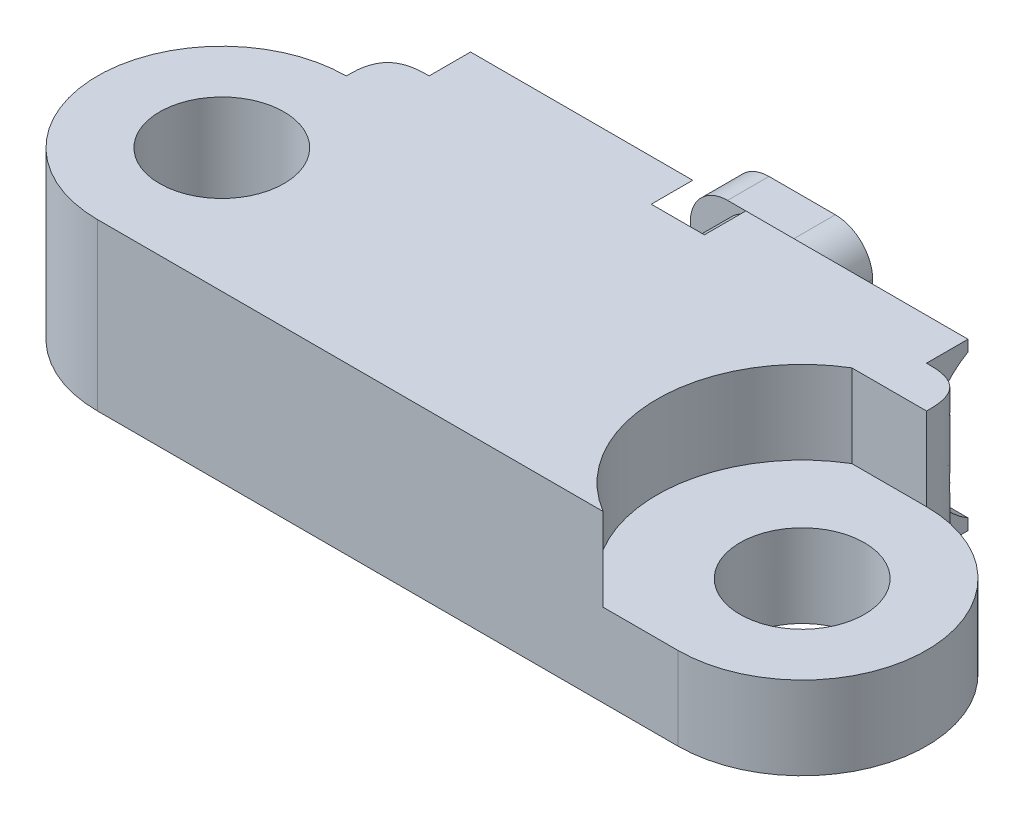
SolidWorks part; units mm, degrees
ref_plane "Front Plane" through (0, 0, 0) normal (0, 0, 1) x (1, 0, 0)
ref_plane "Top Plane" through (0, 0, 0) normal (0, 1, 0) x (1, 0, 0)
ref_plane "Right Plane" through (0, 0, 0) normal (1, 0, 0) x (0, 0, -1)
sketch "Sketch1" plane through (0, 0, 0) normal (0, 1, 0) x (1, 0, 0)
  line L0 (-7, 0) -> (7, 0) construction
  line L1 (-7, 3) -> (7, 3)
  line L2 (-7, -3) -> (7, -3)
  arc A0 (-7, 3) -> (-7, -3) centre (-7, 0) ccw
  arc A1 (7, -3) -> (7, 3) centre (7, 0) ccw
  circle A2 centre (-7, 0) radius 1.5
  circle A3 centre (7, 0) radius 1.5
  point P3 (0, 0)
  point P9 (-10, 0)
  point P10 (10, 0)
  dimension "D3" = 3
  dimension "D4" = 3
  dimension "D1" = 6
  dimension "D2" = 20
extrude "Boss-Extrude1" add sketch "Sketch1" along normal mid plane 4
sketch "Sketch2" plane through (0, 2, 0) normal (0, 1, 0) x (1, 0, 0)
  line L0 (5.1972, 3) -> (7, 3)
  line L1 (7, 3) -> (-7, 3) construction
  line L2 (-7, -3) -> (7, -3) construction
  line L3 (7, -3) -> (5.1972, -3)
  arc A0 (7, 3) -> (7, -3) centre (7, 0) cw
  arc A1 (5.1972, -3) -> (5.1972, 3) centre (7, 0) cw
  dimension "D1" = 3.5
extrude "Cut-Extrude1" cut sketch "Sketch2" against normal blind 2
sketch "Sketch3" plane through (0, -2, 0) normal (0, -1, 0) x (1, 0, 0)
  line L0 (7, -3) -> (7, -4)
  line L1 (7, -4) -> (-7, -4)
  line L2 (-7, -4) -> (-7, -3)
  line L3 (-7, -3) -> (7, -3)
  dimension "D1" = 1
extrude "Boss-Extrude2" add sketch "Sketch3" against normal up to surface (4 mm away) up to face at (-2.0757, 2, 0)
fillet "Fillet1" radius 1 2 edges at (7, 0, -4) (-7, 0, -4) curvature continuous yes
sketch "Sketch4" plane through (0, 0, 0) normal (1, 0, 0) x (0, 0, -1)
  line L0 (4, 0) -> (6, 0) construction
  line L2 (4, 2) -> (6, 2) construction
  line L3 (4, 2) -> (5, 2)
  line L4 (5, 2) -> (5, 1.7321)
  line L5 (5, -2) -> (5, -1.7321)
  line L6 (4, -2) -> (5, -2)
  line L7 (4, 2) -> (4, -2)
  arc A1 (5, -1.7321) -> (5, 1.7321) centre (6, 0) cw
  dimension "D2" = 2
  dimension "D1" = 1
extrude "Boss-Extrude3" add sketch "Sketch4" along normal up to vertex (6 mm away) and the other way up to vertex (6 mm away) contours L7 A1 L4 L3 | L5 A1 L7 L6 region at (0, -1.512, -4.3568) region at (0, 1.512, -4.3568) up to point (6, -2, -4) other way up to point (-6, 2, -4)
sketch "Sketch5" plane through (0, 0, 0) normal (0, 0, 1) x (1, 0, 0)
  line L0 (-11.6879, 0) -> (13.8393, 0) construction
  circle A0 centre (0, 0) radius 2.1
  dimension "D1" = 4.2
extrude "Cut-Extrude4" cut sketch "Sketch5" against normal blind 10 from vertex starting at point (6, 0, -4)
sketch "Sketch6" plane through (0, 0, -4) normal (0, 0, -1) x (-1, 0, 0)
  line L0 (0, 1) -> (-0.8, 1)
  line L1 (-1.7, 0.1) -> (-1.7, -0.1)
  line L2 (-0.8, -1) -> (0, -1)
  line L3 (0, -1) -> (0.8, -1)
  line L4 (1.7, -0.1) -> (1.7, 0.1)
  line L5 (0.8, 1) -> (0, 1)
  circle A0 centre (0, 0) radius 1
  arc A1 (1.7, 0.1) -> (0.8, 1) centre (0.8, 0.1) ccw
  arc A2 (0.8, -1) -> (1.7, -0.1) centre (0.8, -0.1) ccw
  arc A3 (-1.7, -0.1) -> (-0.8, -1) centre (-0.8, -0.1) ccw
  arc A4 (-0.8, 1) -> (-1.7, 0.1) centre (-0.8, 0.1) ccw
  point P17 (-1.7, 1)
  dimension "D1" = 2
  dimension "D3" = 0.9
  dimension "D2" = 0.8
  dimension "D4" = 0.8
extrude "Boss-Extrude5" add sketch "Sketch6" along normal blind 3 contours A0 region at (0, 0, -4)
extrude "Boss-Extrude6" add sketch "Sketch6<3>" along normal blind 1 from offset 2 contours L3 A2 L4 A1 L5 A0 | L0 A4 L1 A3 L2 A0 region at (1.1489, 0, -4) region at (-1.1489, 0, -4)
sketch "Sketch6<3>" plane through (0, 0, -4) normal (0, 0, -1) x (-1, 0, 0) same geometry as "Sketch6"
